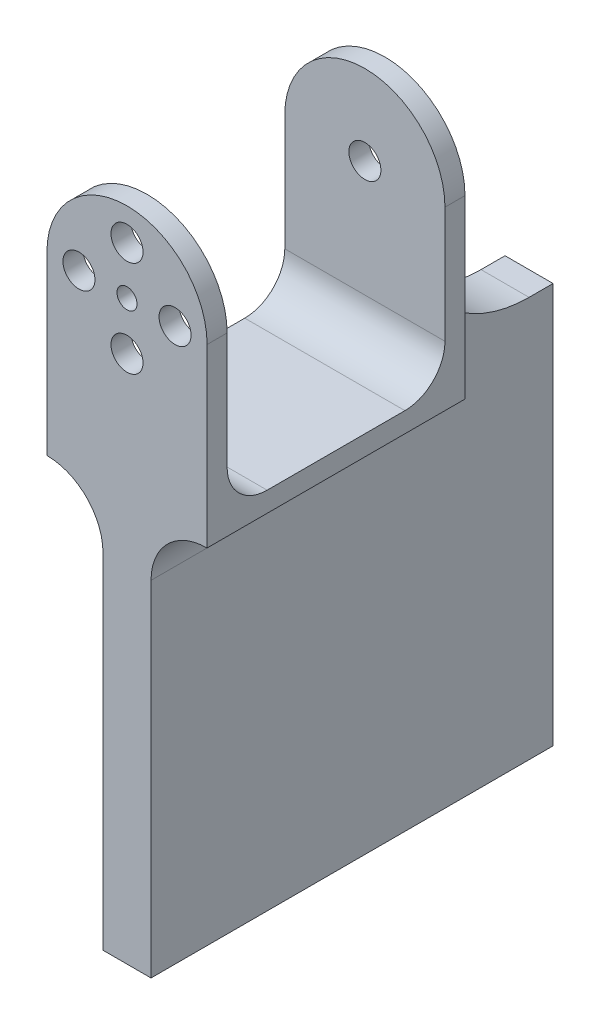
SolidWorks part; units mm, degrees
material "ABS"
ref_plane "Front Plane" through (0, 0, 0) normal (0, 0, 1) x (1, 0, 0)
ref_plane "Top Plane" through (0, 0, 0) normal (0, 1, 0) x (1, 0, 0)
ref_plane "Right Plane" through (0, 0, 0) normal (1, 0, 0) x (0, 0, -1)
sketch "Sketch2" plane through (0, 0, 0) normal (0, 0, -1) x (-1, 0, 0)
  circle A0 centre (0, 0) radius 10
  dimension "D1" = 20
extrude "Boss-Extrude1" add sketch "Sketch2" against normal blind 2.5
sketch "Sketch4" plane through (0, 0, 0) normal (0, 0, -1) x (-1, 0, 0)
  circle A0 centre (0, 0) radius 1.25
  dimension "D1" = 2.5
extrude "Cut-Extrude3" cut sketch "Sketch4" against normal blind 10
sketch "Sketch5" plane through (0, 0, 0) normal (0, 0, -1) x (-1, 0, 0)
  circle A0 centre (0, 6) radius 2
  dimension "D1" = 4
  dimension "D2" = 6
extrude "Cut-Extrude4" cut sketch "Sketch5" against normal blind 10
pattern_circular "CirPattern1" count 4 over 360 about axis through (0, 0, 0) along (0, 0, -1) of "Cut-Extrude4"
sketch "Sketch6" plane through (0, 0, 2.5) normal (0, 0, 1) x (1, 0, 0)
  line L2 (-10, 0) -> (-10, -22)
  line L3 (-10, -22) -> (10, -22)
  line L4 (10, 0) -> (10, -22)
  circle A0 centre (0, 0) radius 10 construction
  arc A1 (-10, 0) -> (10, 0) centre (0, 0) ccw
  dimension "D1" = 22
extrude "Boss-Extrude2" add sketch "Sketch6" against normal up to surface (2.5 mm away) up to face at (6, 2, 0)
sketch "Sketch8" plane through (0, 0, 0) normal (0, 0, -1) x (-1, 0, 0)
  line L0 (-10, -22) -> (-10, 0) construction
  line L1 (10, -22) -> (-10, -22)
  line L2 (10, -22) -> (10, -19.5)
  line L3 (10, -19.5) -> (-10, -19.5)
  line L4 (-10, -22) -> (-10, -19.5)
  dimension "D1" = 2.5
extrude "Boss-Extrude3" add sketch "Sketch8" along normal blind 27.2
sketch "Sketch10" plane through (0, 0, -27.2) normal (0, 0, -1) x (-1, 0, 0)
  line L0 (-10, -22) -> (10, -22) construction
  line L1 (-10, -22) -> (10, -22)
  line L2 (10, 0) -> (10, -22)
  line L3 (-10, -19.5) -> (10, -19.5)
  line L4 (10, -19.5) -> (10, 0)
  line L5 (-10, 0) -> (-10, -19.5)
  line L9 (-10, 0) -> (-10, -22)
  arc A1 (10, 0) -> (-10, 0) centre (0, 0) ccw
  arc A2 (10, 0) -> (-10, 0) centre (0, 0) ccw
  circle A6 centre (0, 0) radius 2
  circle A7 centre (0, -6) radius 2 construction
  dimension "D1" = 0
extrude "Boss-Extrude4" add sketch "Sketch10" along normal blind 2.5
fillet "Fillet1" radius 5 2 edges at (0, -19.5, 0) (0, -19.5, -27.2)
sketch "Sketch12" plane through (0, -22, 0) normal (0, -1, 0) x (1, 0, 0)
  line L1 (3, -29.7) -> (-3, -29.7)
  line L2 (3, -29.7) -> (3, 2.5)
  line L3 (3, 2.5) -> (-3, 2.5)
  line L4 (-3, -29.7) -> (-3, 2.5)
  line L5 (-10, 2.5) -> (10, 2.5) construction
  line L6 (10, -29.7) -> (10, 2.5) construction
  line L7 (-10, -29.7) -> (-10, 2.5) construction
  line L11 (10, -29.7) -> (-10, -29.7) construction
  dimension "D1" = 7
  dimension "D2" = 7
extrude "Boss-Extrude5" add sketch "Sketch12" along normal blind 50
sketch "Sketch13" plane through (0, 0, -29.7) normal (0, 0, -1) x (-1, 0, 0)
  line L0 (3, -72) -> (3, -22) construction
  line L1 (-3, -72) -> (3, -72)
  line L2 (-3, -72) -> (-3, -22)
  line L3 (-3, -22) -> (3, -22)
  line L4 (3, -72) -> (3, -22)
  line L6 (-10, -22) -> (-3, -22) construction
extrude "Boss-Extrude6" add sketch "Sketch13" along normal blind 18
fillet "Fillet2" radius 7 2 edges at (-3, -22, -13.6) (3, -22, -13.6)
fillet "Fillet3" radius 15 1 edges at (0, -22, -29.7)
